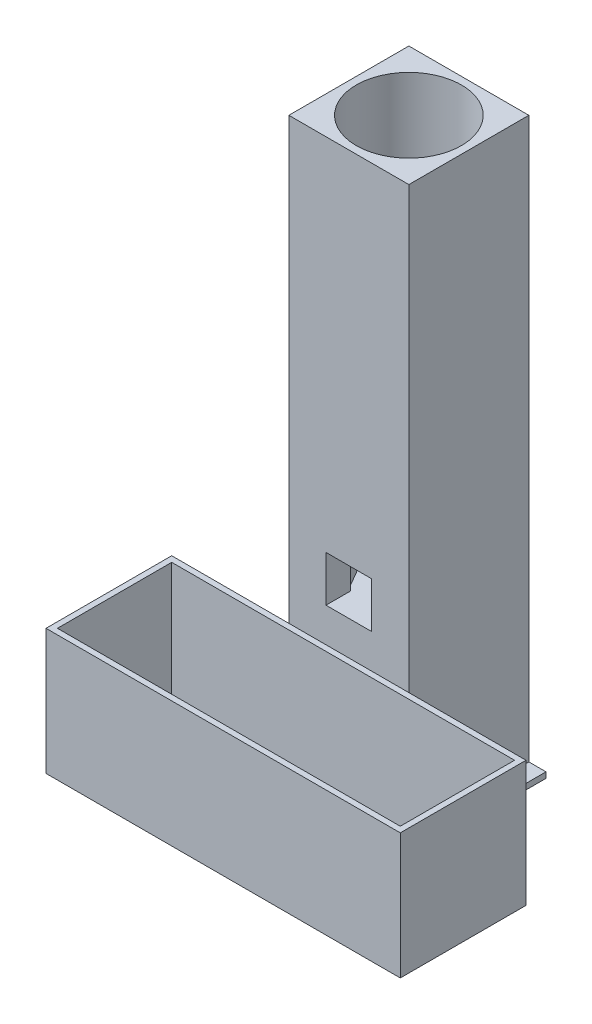
SolidWorks part; units mm, degrees
ref_plane "Front Plane" through (0, 0, 0) normal (0, 0, 1) x (1, 0, 0)
ref_plane "Top Plane" through (0, 0, 0) normal (0, 1, 0) x (1, 0, 0)
ref_plane "Right Plane" through (0, 0, 0) normal (1, 0, 0) x (0, 0, -1)
sketch "Sketch2" plane through (0, 0, 0) normal (0, 1, 0) x (1, 0, 0)
  line L0 (-7.1, 17.2376) -> (7.1, 17.2376)
  line L1 (11.3782, 14.7676) -> (18.4782, 2.47)
  line L2 (18.4782, -2.47) -> (11.3782, -14.7676)
  line L3 (7.1, -17.2376) -> (-7.1, -17.2376)
  line L4 (-11.3782, -14.7676) -> (-18.4782, -2.47)
  line L5 (-18.4782, 2.47) -> (-11.3782, 14.7676)
  line L6 (-7.1, 17.2376) -> (-11.3782, 14.7676)
  line L7 (11.3782, 14.7676) -> (7.1, 17.2376)
  line L8 (18.4782, -2.47) -> (18.4782, 2.47)
  line L9 (7.1, -17.2376) -> (11.3782, -14.7676)
  line L10 (-11.3782, -14.7676) -> (-7.1, -17.2376)
  line L11 (-18.4782, 2.47) -> (-18.4782, -2.47)
  line L13 (-26.25, -26.25) -> (26.25, -26.25)
  line L14 (-26.25, -26.25) -> (-26.25, 26.25)
  line L15 (-26.25, 26.25) -> (26.25, 26.25)
  line L16 (26.25, -26.25) -> (26.25, 26.25)
  line L17 (-26.25, -26.25) -> (26.25, 26.25) construction
  line L18 (-26.25, 26.25) -> (26.25, -26.25) construction
  circle A0 centre (0, 0) radius 28.6425
  circle A1 centre (0, 0) radius 18.6425 construction
  circle A2 centre (0, 0) radius 23
  point P5 (0, 17.2376)
  point P16 (0, 0)
  dimension "D5" = 10
  dimension "D6" = 46
  dimension "D7" = 52.5
  dimension "D1" = 14.2
  dimension "D2" = 4.94
  dimension "D3" = 6
  dimension "D8" = 52.5
  dimension "D4" = 6
extrude "Boss-Extrude1" add sketch "Sketch2" along normal blind 50 contours A0 A2 | A2 L11 L5 L6 L0 L7 L1 L8 L2 L9 L3 L10 L4 region at (-19.7283, 0, 19.7283) region at (-22.3495, 0, 0)
extrude "Boss-Extrude2" add sketch "Sketch2<3>" along normal blind 127.5 from surface contours A0 A2 region at (-19.7283, 0, 19.7283) starting at face at (0, 50, 0)
sketch "Sketch2<3>" plane through (0, 0, 0) normal (0, 1, 0) x (1, 0, 0) same geometry as "Sketch2"
extrude "Boss-Extrude3" add sketch "Sketch2<4>" along normal up to surface (177.5 mm away) contours A0 L15 L14 | A0 L16 L15 | A0 L13 L16 | A0 L14 L13 region at (-21.968, 0, 21.968) region at (21.968, 0, 21.968) region at (-21.968, 0, -21.968) region at (21.968, 0, -21.968) up to face at (0, 177.5, 0)
sketch "Sketch2<4>" plane through (0, 0, 0) normal (0, 1, 0) x (1, 0, 0) same geometry as "Sketch2"
sketch "Sketch3" plane through (0, 0, 0) normal (0, -1, 0) x (1, 0, 0)
  line L1 (-26.25, 26.25) -> (26.25, 26.25)
  line L2 (-26.25, 26.25) -> (-26.25, -26.25)
  line L3 (-26.25, -26.25) -> (26.25, -26.25)
  line L4 (26.25, 26.25) -> (26.25, -26.25)
extrude "Boss-Extrude4" add sketch "Sketch3" along normal blind 70
ref_plane "Plane1" through (0, -70, 0) normal (0, -1, 0) x (-1, 0, 0)
sketch "Sketch4" plane through (0, -70, 0) normal (0, -1, 0) x (-1, 0, 0)
  line L0 (-26.25, -26.25) -> (26.25, -26.25) construction
  line L1 (77.5, -26.25) -> (-77.5, -26.25)
  line L2 (77.5, -26.25) -> (77.5, -81.25)
  line L3 (77.5, -81.25) -> (-77.5, -81.25)
  line L4 (-77.5, -26.25) -> (-77.5, -81.25)
  line L6 (75, -28.75) -> (-75, -28.75)
  line L7 (75, -28.75) -> (75, -78.75)
  line L8 (75, -78.75) -> (-75, -78.75)
  line L9 (-75, -28.75) -> (-75, -78.75)
  point P5 (0, -26.25)
  point P13 (0, -28.75)
  dimension "D1" = 155
  dimension "D2" = 55
  dimension "D3" = 2.5
  dimension "D4" = 150
  dimension "D5" = 50
extrude "Boss-Extrude5" add sketch "Sketch4" against normal blind 2.5 separate body contours L7 L6 L9 L8
extrude "Boss-Extrude6" add sketch "Sketch4<4>" against normal blind 55
sketch "Sketch4<4>" plane through (0, -70, 0) normal (0, -1, 0) x (-1, 0, 0) same geometry as "Sketch4"
sketch "Sketch5" plane through (0, -70, 0) normal (0, -1, 0) x (1, 0, 0)
  line L1 (-26.25, -26.25) -> (26.25, -26.25) construction
  line L2 (-26.25, -26.25) -> (-26.25, 26.25) construction
  line L3 (-26.25, 26.25) -> (26.25, 26.25) construction
  line L4 (26.25, -26.25) -> (26.25, 26.25) construction
  line L5 (-26.25, -26.25) -> (26.25, 26.25) construction
  line L6 (-26.25, 26.25) -> (26.25, -26.25) construction
  line L7 (-23.75, -23.75) -> (23.75, -23.75)
  line L8 (-23.75, -23.75) -> (-23.75, 23.75)
  line L9 (-23.75, 23.75) -> (23.75, 23.75)
  line L10 (23.75, -23.75) -> (23.75, 23.75)
  line L11 (-23.75, -23.75) -> (23.75, 23.75) construction
  line L12 (-23.75, 23.75) -> (23.75, -23.75) construction
  point P0 (0, 0)
  point P8 (0, 0)
  dimension "D1" = 2.5
extrude "Cut-Extrude4" cut sketch "Sketch5" against normal blind 50
sketch "Sketch6" plane through (0, 0, 26.25) normal (0, 0, 1) x (1, 0, 0)
  line L0 (59.125, 0) -> (-59.125, 0) construction
  line L1 (10, 20) -> (-10, 20)
  line L2 (10, 20) -> (10, 0)
  line L3 (10, 0) -> (-10, 0)
  line L4 (-10, 20) -> (-10, 0)
  point P6 (0, 20)
  dimension "D1" = 20
  dimension "D2" = 20
extrude "Cut-Extrude5" cut sketch "Sketch6" against normal blind 20
sketch "Sketch7" plane through (0, -70, 0) normal (0, -1, 0) x (1, 0, 0)
  line L0 (-33.75, 26.25) -> (-33.75, -26.25)
  line L1 (-33.75, 26.25) -> (33.75, 26.25)
  line L2 (-33.75, -26.25) -> (33.75, -26.25)
  line L3 (33.75, 26.25) -> (33.75, -26.25)
  line L4 (-33.75, 26.25) -> (33.75, -26.25) construction
  line L5 (-33.75, -26.25) -> (33.75, 26.25) construction
  line L6 (-26.25, 26.25) -> (-26.25, -26.25) construction
  line L7 (-26.25, -26.25) -> (26.25, -26.25) construction
  line L8 (85.25, 0) -> (-85.25, 0) construction
  line L9 (0, -1000) -> (0, 49000) construction
  circle A0 centre (-30, 0) radius 1.65
  circle A1 centre (30, 0) radius 1.65
  point P1 (0, 0)
  line M9 (-26.25, 26.25) -> (-26.25, -26.25)
  line M11 (26.25, -26.25) -> (26.25, 26.25)
  line M12 (26.25, 26.25) -> (77.5, 26.25)
  line M16 (-77.5, 26.25) -> (-26.25, 26.25)
  dimension "D2" = 3.3
  dimension "D1" = 7.5
  dimension "D3" = 3.75
extrude "Boss-Extrude7" add sketch "Sketch7" against normal blind 2.5 contours L0 L2 M9 M16 | L3 L2 M12 M11 region at (-30, -70, 25.7197) region at (30, -70, 25.7197)
